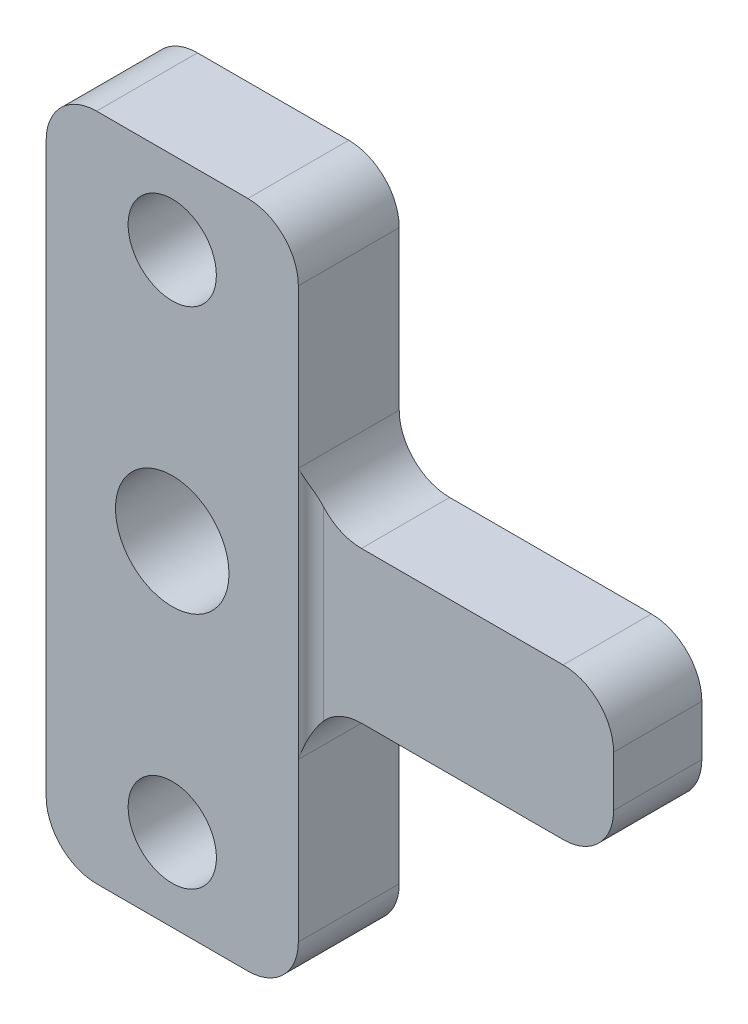
SolidWorks part; units mm, degrees
ref_plane "Front Plane" through (0, 0, 0) normal (0, 0, 1) x (1, 0, 0)
ref_plane "Top Plane" through (0, 0, 0) normal (0, 1, 0) x (1, 0, 0)
ref_plane "Right Plane" through (0, 0, 0) normal (1, 0, 0) x (0, 0, -1)
sketch "Sketch1" plane through (0, 0, 0) normal (0, 0, 1) x (1, 0, 0)
  line L0 (38, 13.2665) -> (38, -13.2665) construction
  line L1 (33, 13.2665) -> (43, 13.2665)
  line L2 (33, 13.2665) -> (33, -13.2665)
  line L3 (33, -13.2665) -> (43, -13.2665)
  line L4 (43, 13.2665) -> (43, -13.2665)
  line L5 (33, 13.2665) -> (43, -13.2665) construction
  line L6 (33, -13.2665) -> (43, 13.2665) construction
  line L7 (43, 0) -> (33, 0) construction
  line L8 (43, 10) -> (33, 10) construction
  circle A0 centre (0, 0) radius 45 construction
  circle A1 centre (38, 0) radius 2.25
  circle A2 centre (38, 10) radius 1.75
  circle A3 centre (38, -10) radius 1.75
  point P0 (38, 0)
  dimension "D2" = 4.5
  dimension "D3" = 3.5
  dimension "D1" = 10
  dimension "D4" = 10
extrude "Boss-Extrude1" add sketch "Sketch1" along normal blind 4
sketch "Sketch6" plane through (0, 0, 0) normal (0, 0, 1) x (1, 0, 0)
  line L0 (38, 0) -> (55, 0) construction
  line L1 (43, -13.2665) -> (43, 13.2665) construction
  line L2 (55, 3) -> (43, 3)
  line L3 (55, 3) -> (55, -3)
  line L4 (55, -3) -> (43, -3)
  line L5 (43, 3) -> (43, -3)
  point P10 (55, 0)
  dimension "D1" = 6
  dimension "D2" = 12
extrude "Boss-Extrude3" add sketch "Sketch6" along normal blind 3.5
fillet "Fillet1" radius 2 2 edges at (55, -3, 1.75) (55, 3, 1.75)
fillet "Fillet2" radius 2 2 edges at (43, -3, 1.75) (43, 3, 1.75)
fillet "Fillet3" radius 0.5 1 edges at (43, 0, 3.5) type face fillet first side face at (49, 0, 3.5) second side face at (43, 0, 1.875)
fillet "Fillet4" radius 2 4 edges at (43, -13.2665, 2) (33, -13.2665, 2) (33, 13.2665, 2) (43, 13.2665, 2)
